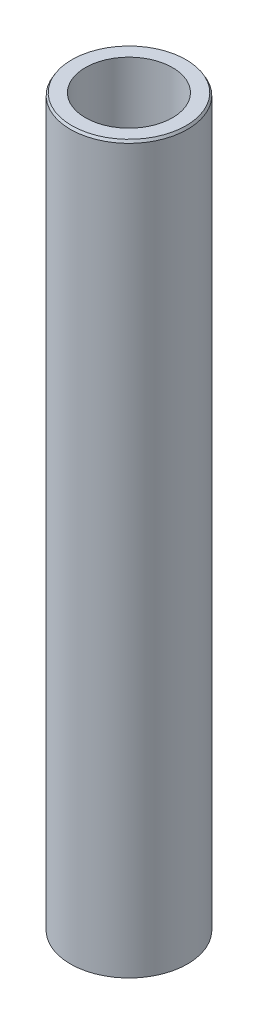
SolidWorks part; units mm, degrees
ref_plane "Front Plane" through (0, 0, 0) normal (0, 0, 1) x (1, 0, 0)
ref_plane "Top Plane" through (0, 0, 0) normal (0, 1, 0) x (1, 0, 0)
ref_plane "Right Plane" through (0, 0, 0) normal (1, 0, 0) x (0, 0, -1)
sketch "Sketch1" plane through (0, 0, 0) normal (0, 1, 0) x (1, 0, 0)
  circle A0 centre (0, 0) radius 27.5
  dimension "SHAFT_OD" = 55
extrude "Boss-Extrude1" add sketch "Sketch1" along normal blind 341.1184
sketch "Sketch2" plane through (0, 0, 0) normal (0, 1, 0) x (1, 0, 0)
  circle A0 centre (0, 0) radius 20.431
  dimension "BORE_D" = 40.862
extrude "Cut-Extrude1" cut sketch "Sketch2" along normal through all
chamfer "Chamfer1" distance 1.1704 angle 30 2 edges at (0, 341.1184, 27.5) (0, 0, 27.5) first distance on face at (0, 341.1184, 27.5) first distance on face at (0, 0, 20.431)
